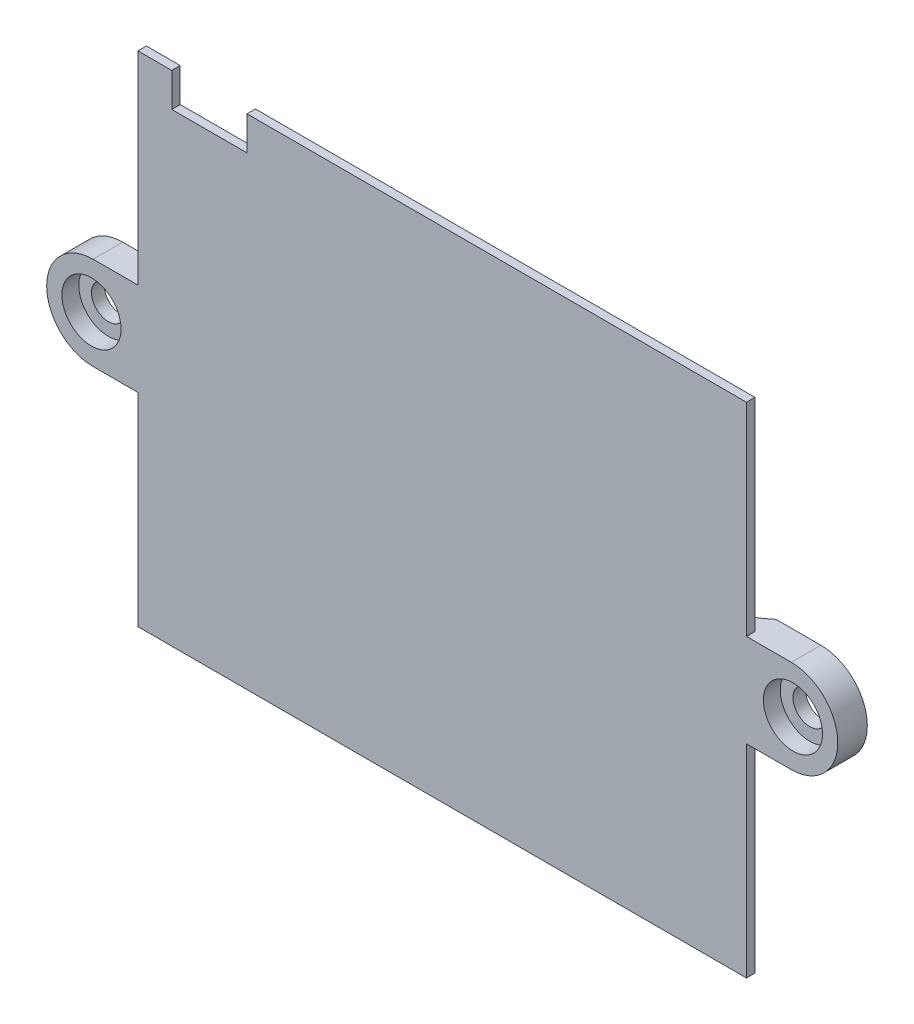
SolidWorks part; units mm, degrees
note: The reader was unsure of these and kept them because the rebuilt part matched: shared geometry of "Sketch1<3>".
ref_plane "Front Plane" through (0, 0, 0) normal (0, 0, 1) x (1, 0, 0)
ref_plane "Top Plane" through (0, 0, 0) normal (0, 1, 0) x (1, 0, 0)
ref_plane "Right Plane" through (0, 0, 0) normal (1, 0, 0) x (0, 0, -1)
sketch "Sketch1" plane through (0, 0, 0) normal (0, 0, 1) x (1, 0, 0)
  line L0 (-103.711, 37.3) -> (-103.711, 33.5) construction
  line L1 (-103.211, -22.2) -> (-31.211, -22.2)
  line L2 (-103.211, -22.2) -> (-103.211, 36.8)
  line L3 (-103.211, 36.8) -> (-31.211, 36.8)
  line L4 (-31.211, -22.2) -> (-31.211, 36.8)
  line L5 (-30.711, 37.3) -> (-30.711, 33.5) construction
  line L6 (-49.0608, 37.3) -> (-30.711, 37.3) construction
  line L7 (-103.711, -22.7) -> (-30.711, -22.7) construction
  line L8 (-98.911, 7.3) -> (-108.511, 7.3) construction
  line L9 (-99.211, 37.3) -> (-99.211, 46.9901) construction
  line L10 (-103.711, 13.3) -> (-103.711, 1.3) construction
  line L11 (-98.911, 1.8) -> (-108.511, 1.8)
  line L12 (-98.911, 12.8) -> (-108.511, 12.8)
  line L13 (-67.211, 36.8) -> (-67.211, -22.2) construction
  line L14 (-35.511, 7.3) -> (-25.911, 7.3) construction
  line L15 (-35.511, 1.8) -> (-25.911, 1.8)
  line L16 (-35.511, 12.8) -> (-25.911, 12.8)
  line L17 (-103.711, 13.3) -> (-108.711, 13.3) construction
  line L18 (-99.211, 36.8) -> (-90.311, 36.8)
  line L19 (-99.211, 36.8) -> (-99.211, 32.8)
  line L20 (-99.211, 32.8) -> (-90.311, 32.8)
  line L21 (-90.311, 36.8) -> (-90.311, 32.8)
  line L22 (-90.311, 43.45) -> (-90.311, 46.9901) construction
  arc A0 (-98.911, 1.8) -> (-98.911, 12.8) centre (-98.911, 7.3) ccw
  arc A1 (-108.511, 12.8) -> (-108.511, 1.8) centre (-108.511, 7.3) ccw
  arc A2 (-35.511, 1.8) -> (-35.511, 12.8) centre (-35.511, 7.3) cw
  arc A3 (-25.911, 12.8) -> (-25.911, 1.8) centre (-25.911, 7.3) cw
  arc A4 (-108.711, 13.3) -> (-108.711, 1.3) centre (-108.711, 7.3) ccw construction
  circle A5 centre (-108.711, 7.3) radius 2
  circle A6 centre (-25.711, 7.3) radius 2
  point P16 (-103.711, 7.3)
  point P25 (-30.711, 7.3)
  dimension "D6" = 0.2
  dimension "D7" = 4
  dimension "D1" = 0.5
  dimension "D2" = 0.5
  dimension "D3" = 0.5
  dimension "D4" = 0.5
  dimension "D5" = 0.5
  dimension "D8" = 4
extrude "Boss-Extrude1" add sketch "Sketch1" against normal blind 1 from surface contours L15 A2 L16 L4 L3 L2 L12 A0 L11 L1 | L11 A0 L12 L2 | A2 L15 L4 L16
extrude "Boss-Extrude2" add sketch "Sketch1<3>" against normal offset from surface (3.5 mm away) 0.5 from surface contours L12 A1 L11 L2 A5 | A3 L16 L4 L15 A6
sketch "Sketch1<3>" plane through (0, 0, 0) normal (0, 0, 1) x (1, 0, 0) same geometry as "Sketch1"
fillet "Fillet1" radius 10 2 edges at (-31.211, 7.3, 3) (-103.211, 7.3, 3)
sketch "Sketch2" plane through (0, 0, 4) normal (0, 0, 1) x (1, 0, 0)
  circle A0 centre (-108.711, 7.3) radius 3.5
  circle A1 centre (-25.711, 7.3) radius 3.5
  dimension "D1" = 7
extrude "Cut-Extrude1" cut sketch "Sketch2" against normal blind 2
